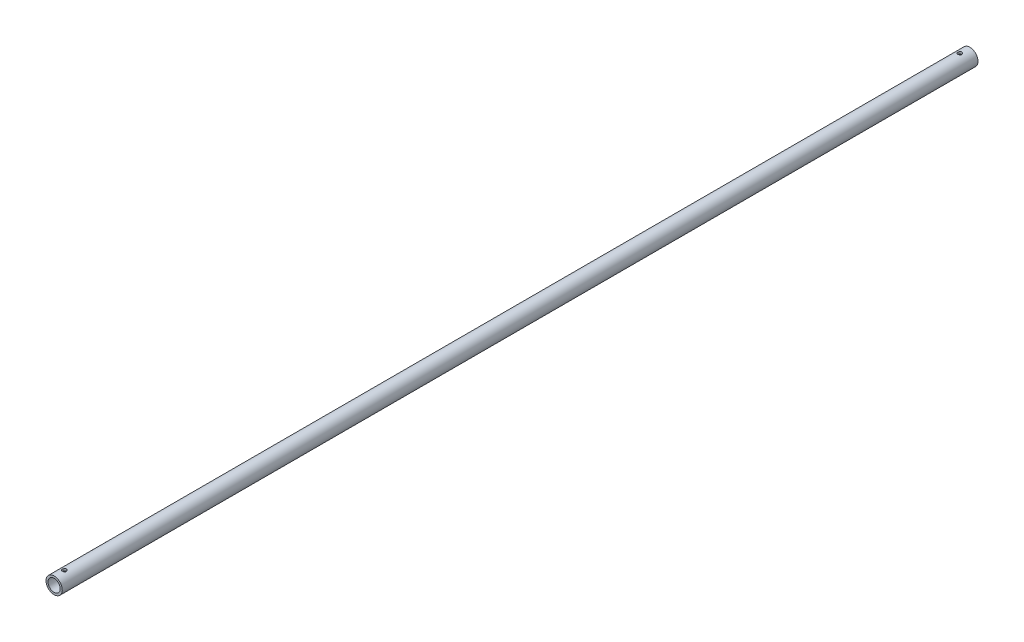
SolidWorks part; units mm, degrees
material "Thornel Mat VMA"
ref_plane "前视基准面" through (0, 0, 0) normal (0, 0, 1) x (1, 0, 0)
ref_plane "上视基准面" through (0, 0, 0) normal (0, 1, 0) x (1, 0, 0)
ref_plane "右视基准面" through (0, 0, 0) normal (1, 0, 0) x (0, 0, -1)
sketch "草图1" plane through (0, 0, 0) normal (0, 0, 1) x (1, 0, 0)
  circle A0 centre (0, 0) radius 3
  circle A1 centre (0, 0) radius 4
  dimension "D1" = 6
  dimension "D2" = 8
extrude "凸台-拉伸1" add sketch "草图1" along normal blind 225 and the other way blind 225
sketch "草图3" plane through (0, 0, 0) normal (0, 1, 0) x (1, 0, 0)
  line L0 (4, 225) -> (-4, 225) construction
  line L1 (-1000, 0) -> (49000, 0) construction
  circle A0 centre (0, 220) radius 1
  circle A1 centre (0, -220) radius 1
  dimension "D1" = 2
  dimension "D2" = 5
extrude "切除-拉伸2" cut sketch "草图3" against normal through all and the other way through all
sketch "草图6" plane through (0, 0, 0) normal (0, 1, 0) x (1, 0, 0)
  circle A0 centre (0, 0) radius 17.2534
